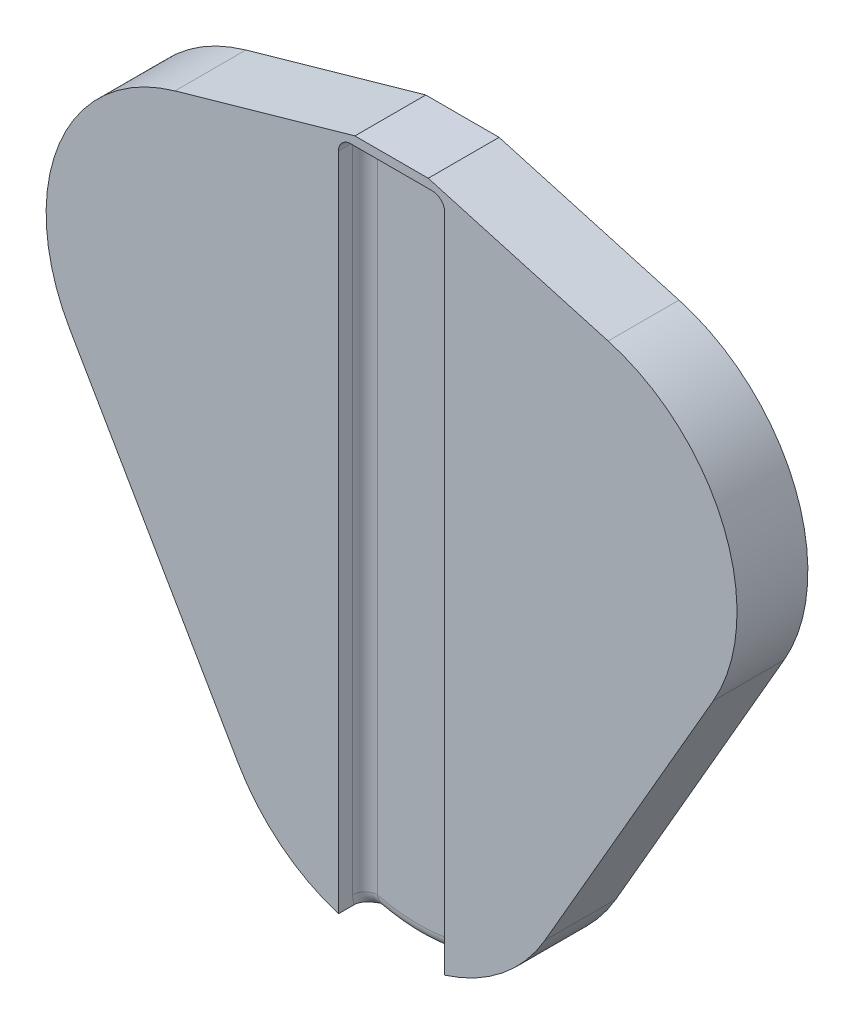
SolidWorks part; units mm, degrees
ref_plane "Front Plane" through (0, 0, 0) normal (0, 0, 1) x (1, 0, 0)
ref_plane "Top Plane" through (0, 0, 0) normal (0, 1, 0) x (1, 0, 0)
ref_plane "Right Plane" through (0, 0, 0) normal (1, 0, 0) x (0, 0, -1)
sketch "Sketch1" plane through (0, 0, 0) normal (0, 0, 1) x (1, 0, 0)
  line L0 (-200000, 0) -> (200119.5956, 0) construction
  line L1 (0, -200000) -> (0, 200075.1119) construction
  line L2 (-2.0695, 17.9848) -> (-12.2269, 15.1058) construction
  line L3 (-2.0695, 17.9848) -> (2.0695, 17.9848) construction
  line L4 (2.0695, 17.9848) -> (12.2269, 15.1058) construction
  line L5 (8.6603, -15.9697) -> (18.1603, 0.4848) construction
  line L6 (-8.6603, -15.9697) -> (-18.1603, 0.4848) construction
  line L7 (-200000, 0) -> (200119.5956, 0)
  line L8 (0, -200000) -> (0, 200075.1119)
  line L9 (-2.0695, 17.9848) -> (-12.2269, 15.1058)
  line L10 (-2.0695, 17.9848) -> (2.0695, 17.9848)
  line L11 (2.0695, 17.9848) -> (12.2269, 15.1058)
  line L12 (8.6603, -15.9697) -> (18.1603, 0.4848)
  line L13 (-8.6603, -15.9697) -> (-18.1603, 0.4848)
  arc A0 (18.1603, 0.4848) -> (12.2269, 15.1058) centre (9.5, 5.4848) ccw construction
  arc A1 (-8.6603, -15.9697) -> (8.6603, -15.9697) centre (0, -10.9697) ccw construction
  arc A2 (-12.2269, 15.1058) -> (-18.1603, 0.4848) centre (-9.5, 5.4848) ccw construction
  arc A3 (18.1603, 0.4848) -> (12.2269, 15.1058) centre (9.5, 5.4848) ccw
  arc A4 (-8.6603, -15.9697) -> (8.6603, -15.9697) centre (0, -10.9697) ccw
  arc A5 (-12.2269, 15.1058) -> (-18.1603, 0.4848) centre (-9.5, 5.4848) ccw
extrude "Boss-Extrude1" add sketch "Sketch1" along normal up to surface (4 mm away) from surface contours A5 L13 A4 L12 A3 L11 L10 L9
sketch "Sketch2" plane through (0, 0, 0) normal (0, 1, 0) x (1, 0, 0)
  line L0 (3, 31.5) -> (3, 36.5) construction
  line L1 (-3, 31.5) -> (3, 31.5) construction
  line L2 (-3, 36.5) -> (-3, 31.5) construction
  line L3 (3, 31.5) -> (3, 36.5)
  line L4 (-3, 31.5) -> (3, 31.5)
  line L5 (-3, 36.5) -> (-3, 31.5)
  line L6 (-3, 34) -> (3, 34)
  line L7 (-2.0695, 32.5) -> (2.0695, 32.5) construction
  dimension "D1" = 1.5
extrude "Cut-Extrude1" cut sketch "Sketch2" against normal through all and the other way up to surface contours L6 L5 L4 L3
sketch "Sketch4" plane through (0, 0, -36.5) normal (0, 0, -1) x (-1, 0, 0)
  line L0 (9, -13) -> (9, -3) construction
  line L1 (9, -3) -> (5, -3) construction
  line L2 (5, -3) -> (5, -8) construction
  line L3 (5, -8) -> (-5, -8) construction
  line L4 (-5, -8) -> (-5, -3) construction
  line L5 (-5, -3) -> (-9, -3) construction
  line L6 (-9, -3) -> (-9, -13) construction
  line L7 (-9, -13) -> (9, -13) construction
  line L8 (9.1, -13.1) -> (9.1, -2.9)
  line L9 (9.1, -2.9) -> (4.9, -2.9)
  line L10 (4.9, -2.9) -> (4.9, -7.9)
  line L11 (4.9, -7.9) -> (-4.9, -7.9)
  line L12 (-4.9, -7.9) -> (-4.9, -2.9)
  line L13 (-4.9, -2.9) -> (-9.1, -2.9)
  line L14 (-9.1, -2.9) -> (-9.1, -13.1)
  line L15 (-9.1, -13.1) -> (9.1, -13.1)
  dimension "D1" = 0.1
extrude "Cut-Extrude2" cut sketch "Sketch4" against normal blind 2 contours L14 L15 L8 L9 L10 L11 L12 L13
fillet "Fillet1" radius 0.7 4 edges at (0, -20.9697, -34) (-3, 17.4848, -33.25) (3, 17.4848, -33.25) (0, 17.4848, -34)
fillet "Fillet2" radius 0.7 6 edges at (3, -20.2523, -34.1684) (2.795, 17.2798, -33.795) (-3, -20.3607, -34.2781) (-2.795, 17.2798, -33.795) (3, -1.4938, -34) (-3, -1.4938, -34)
